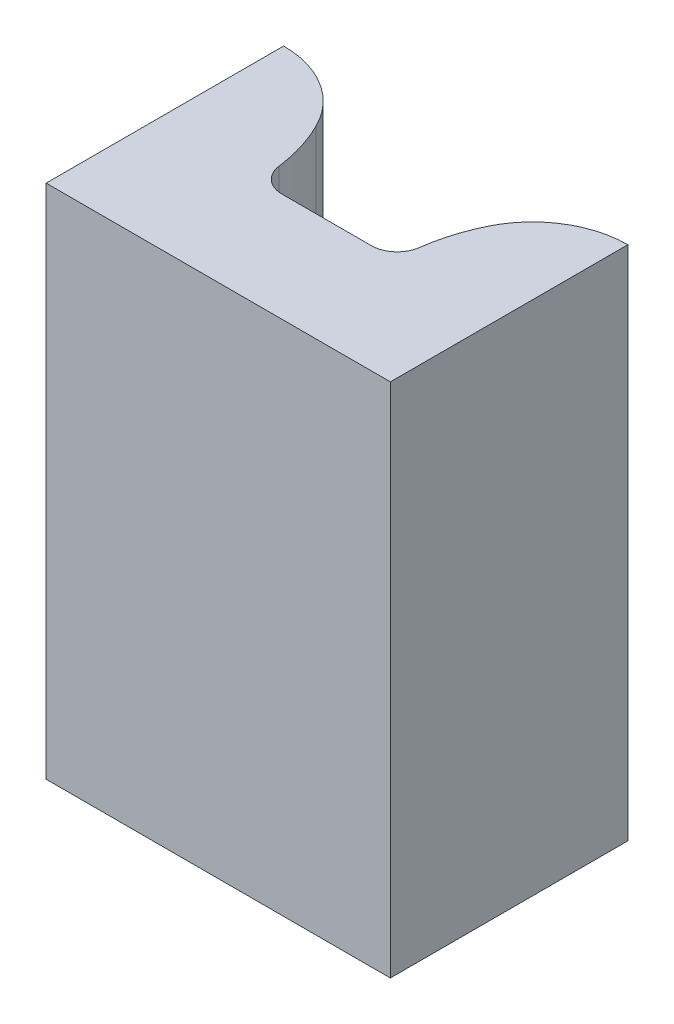
SolidWorks part; units mm, degrees
ref_plane "Płaszczyzna przednia" through (0, 0, 0) normal (0, 0, 1) x (1, 0, 0)
ref_plane "Płaszczyzna górna" through (0, 0, 0) normal (0, 1, 0) x (1, 0, 0)
ref_plane "Płaszczyzna prawa" through (0, 0, 0) normal (1, 0, 0) x (0, 0, -1)
sketch "Sketch1" plane through (0, 0, 0) normal (0, 1, 0) x (1, 0, 0)
  line L0 (0, 0) -> (2, 0)
  line L1 (0, 0) -> (0, 1.38)
  line L2 (2, 0) -> (2, 1.38)
  line L3 (0, 0.376) -> (2, 0.376) construction
  line L4 (-0.4, 0.63) -> (2.4, 0.63) construction
  line L5 (2.4, 1.38) -> (2.4, 0) construction
  line L6 (-0.4, 1.38) -> (-0.4, 0) construction
  line L7 (2, 0.825) -> (0, 0.825) construction
  line L8 (1, 0) -> (1, 1.5077) construction
  line L9 (0.7402, 0.63) -> (1.2598, 0.63)
  arc A0 (1.5011, 1.0682) -> (1.4085, 0.7604) centre (2.4, 0.63) ccw
  arc A1 (0.5915, 0.7604) -> (0.4989, 1.0682) centre (-0.4, 0.63) ccw
  arc A2 (2, 1.38) -> (1.5011, 1.0682) centre (2, 0.825) ccw
  arc A4 (0.5915, 0.7604) -> (0.7402, 0.63) centre (0.7402, 0.78) ccw
  arc A5 (1.4085, 0.7604) -> (1.2598, 0.63) centre (1.2598, 0.78) cw
  arc A6 (0.4989, 1.0682) -> (0, 1.38) centre (0, 0.825) ccw
  dimension "D6" = 2
  dimension "D8" = 2
  dimension "D9" = 1.11
  dimension "D12" = 0.3
  dimension "D1" = 2
  dimension "D2" = 1.38
  dimension "D3" = 1.004
  dimension "D4" = 0.254
  dimension "D5" = 0.4
  dimension "D7" = 0.4
  dimension "D10" = 0.555
extrude "Boss-Extrude1" add sketch "Sketch1" along normal mid plane 3
ref_plane "Plane1" through (0, 0, 0) normal (0, 0, 1) x (1, 0, 0)
